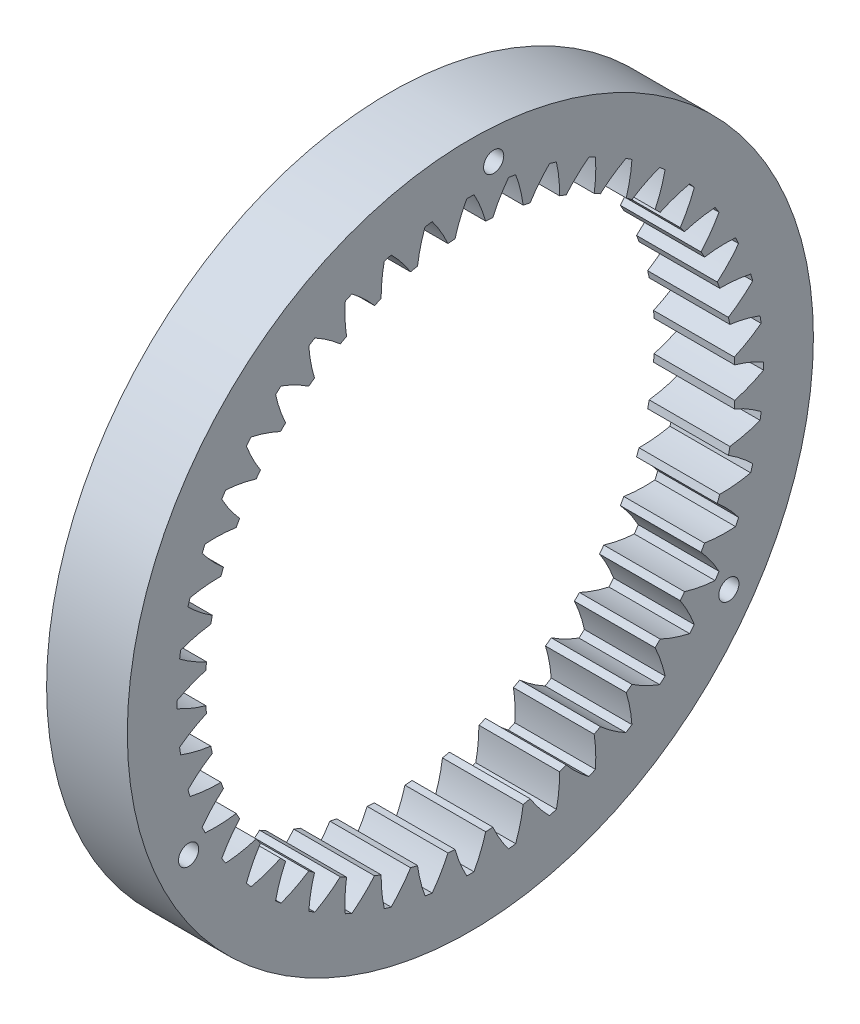
SolidWorks part; units mm, degrees
ref_plane "Plane1" through (0, 0, 0) normal (0, 0, 1) x (1, 0, 0)
ref_plane "Plane2" through (0, 0, 0) normal (0, 1, 0) x (1, 0, 0)
ref_plane "Plane3" through (0, 0, 0) normal (1, 0, 0) x (0, 0, -1)
sketch "HoldingSke" plane through (0, 0, 0) normal (0, 1, 0) x (1, 0, 0)
  line L0 (0, 0) -> (0.5755, -0.5557)
  line L1 (-15, 0) -> (100, 0) construction
  line L2 (0, 0) -> (-2.1039, 2.3779)
  line L3 (0, 0) -> (-11.863, 4.5341)
  line L4 (0, 0) -> (6.2122, 5.9991)
  line L5 (0, 0) -> (-23.7986, -8.8762)
  line L6 (0, 0) -> (-10.5278, -7.1032)
  line L7 (-2.1039, 2.3779) -> (3.3635, 27.1825)
  line L8 (-76.2, 3.6279) -> (-54.61, 3.6279)
  line L9 (-71.009, 38.7566) -> (-53.1078, 45.2721)
  line L10 (-76.2, 71.12) -> (104.1128, 71.12)
  line L11 (0, 0) -> (-8, 0)
  line L12 (-76.2, 101.6) -> (-76.155, 101.6)
  line L13 (24.9733, 27.94) -> (52.9518, 28.4284)
  line L14 (24.9733, 27.94) -> (24.9743, 27.94)
  line L15 (24.9733, 27.94) -> (100.4006, 29.5858)
  circle A0 centre (0, 0) radius 32.5
  circle A1 centre (0, 0) radius 12.7
  circle A2 centre (0, 0) radius 12.7
  dimension "Num_teeth" = 44
  dimension "Pitch_radius" = 180.3128
  dimension "Width" = 8
sketch "BasProSke" plane through (0, 0, 0) normal (0, 1, 0) x (1, 0, 0)
  line L0 (-10, 0) -> (60, 0) construction
  line L1 (0, 26.25) -> (0, 34)
  line L2 (0, 26.25) -> (8, 26.25)
  line L3 (8, 26.25) -> (8, 34)
  line L4 (8, 34) -> (0, 34)
  dimension "Thickness" = 8
  dimension "Diameter" = 68
revolve "Base-Revolve" add sketch "BasProSke" angle 360 about L0
sketch "TooCutSke" plane through (0, 0, 0) normal (1, 0, 0) x (0, 0, -1)
  line L3 (1.094, 27.4782) -> (1.094, 53.6633) construction
  line L4 (0, 0) -> (0, 59.563) construction
  line L5 (0, 0) -> (-4.8744, 68.1534) construction
  line L6 (-11.7149, 22.4789) -> (36.0872, 25.8978) construction
  circle A0 centre (0, 0) radius 27.5 construction
  circle A1 centre (0, 0) radius 29.0635 construction
  circle A2 centre (0, 0) radius 23.2574 construction
  circle A3 centre (0, 0) radius 26.2246 construction
  arc A4 (1.5276, 26.1801) -> (0.3571, 29.0613) centre (-11.7149, 22.4789) ccw
  arc A5 (1.5276, 26.1801) -> (-1.5276, 26.1801) centre (0, 0) ccw
  arc A6 (0.3571, 29.0613) -> (-0.3571, 29.0613) centre (0, 0) ccw
  arc A7 (-0.3571, 29.0613) -> (-1.5276, 26.1801) centre (11.7149, 22.4789) ccw
extrude "ToothCut" cut sketch "TooCutSke" along normal through all
fillet "Breaks" [suppressed] radius 0.125
fillet "RootFillets" [suppressed] radius 0.3135
pattern_circular "TeethCuts" count 44 every 8.182 about axis through (-10, 0, 0) along (1, 0, 0) of "RootFillets", "Breaks", "ToothCut"
sketch "Skizze1" plane through (8, 0, 0) normal (1, 0, 0) x (0, 0, -1)
  circle A0 centre (2.3107, 30.9138) radius 1
  circle A1 centre (0, 0) radius 34 construction
  dimension "D1" = 2
  dimension "D2" = 31
extrude "Schnitt-Linear austragen1" cut sketch "Skizze1" against normal up to next
pattern_circular "Kreismuster1" count 3 over 360 about axis through (-10, 0, 0) along (-1, 0, 0) of "Schnitt-Linear austragen1"
equation "' \"Module@HoldingSke\" = 6.35"
equation "' \"Num_teeth@HoldingSke\" = 24"
equation "' \"Ap@HoldingSke\" =  14.5"
equation "' \"Ap@HoldingSke\" = 14.5"
equation "' \"Width@HoldingSke\" = 12"
equation "' \"Diameter@HoldingSke\" = 8 * 25.4"
equation "' \"Show_teeth@HoldingSke\" = 100"
equation "' \"Backlash@HoldingSke\" = 0.009 * 25.4"
equation "' \"Addendum_fac@HoldingSke\" = 1.0"
equation "' \"Dedendum_fac@HoldingSke\" = 1.25"
equation "' \"Dedendum_add@HoldingSke\" = 0.00005 * 25.4"
equation "' \"Clearance_fac@HoldingSke\" = 0.25"
equation "\"Pitch@HoldingSke\" = 1 / \"Module@HoldingSke\" "
equation "\"Overcut_dia@TooCutSke\" = (\"Num_teeth@HoldingSke\" - 2 * \"Addendum_fac@HoldingSke\") / \"Pitch@HoldingSke\" - 0.002 * 25.4"
equation "\"Pitch_dia@TooCutSke\" = \"Num_teeth@HoldingSke\" / \"Pitch@HoldingSke\""
equation "\"Base_dia@TooCutSke\" = \"Num_teeth@HoldingSke\" / \"Pitch@HoldingSke\" * cos((\"Ap@HoldingSke\"  * 3.14159265 / 180)) * 0.90"
equation "\"Root_dia@TooCutSke\" = \"Num_teeth@HoldingSke\"  / \"Pitch@HoldingSke\" + 2 *  \"Dedendum_fac@HoldingSke\"/ \"Pitch@HoldingSke\" + \"Dedendum_add@HoldingSke\" * 2"
equation "\"Half_ang@TooCutSke\" = 180 / \"Num_teeth@HoldingSke\""
equation "\"Half_CT@TooCutSke\" = \"Num_teeth@HoldingSke\" / \"Pitch@HoldingSke\" * sin((3.14159265 / 2 / \"Num_teeth@HoldingSke\")) / 2 + 10 * \"Backlash@HoldingSke\" / 4"
equation "\"Flank_rad@TooCutSke\" = \"Num_teeth@HoldingSke\" / \"Pitch@HoldingSke\" / 4"
equation "\"Radius@RootFillets\"= \"Clearance_fac@HoldingSke\" / \"Pitch@HoldingSke\" + \"Dedendum_add@HoldingSke\""
equation "\"Break_rad@Breaks\" = 0.02 / \"Pitch@HoldingSke\" * 5"
equation "\"Num_teeth@TeethCuts\" = int( \"Show_teeth@HoldingSke\" ) + 1"
equation "\"Num_teeth@TeethCuts\" = ((sgn( \"Num_teeth@TeethCuts\" - \"Num_teeth@HoldingSke\" )-1)*( \"Num_teeth@TeethCuts\" - \"Num_teeth@HoldingSke\" ))/-2+ \"Num_teeth@HoldingSke\""
equation "\"Num_teeth@TeethCuts\" = ((sgn( \"Num_teeth@TeethCuts\" - 2.0)+1)*( \"Num_teeth@TeethCuts\" - 2.0))/2 +2.0"
equation "\"Angle@TeethCuts\" = 360.0 / \"Num_teeth@HoldingSke\""
equation "\"Inside_diameter@BasProSke\" =  (\"Num_teeth@HoldingSke\" - 2 * \"Addendum_fac@HoldingSke\") / \"Pitch@HoldingSke\" "
equation "\"Thickness@BasProSke\"  = \"Width@HoldingSke\""
